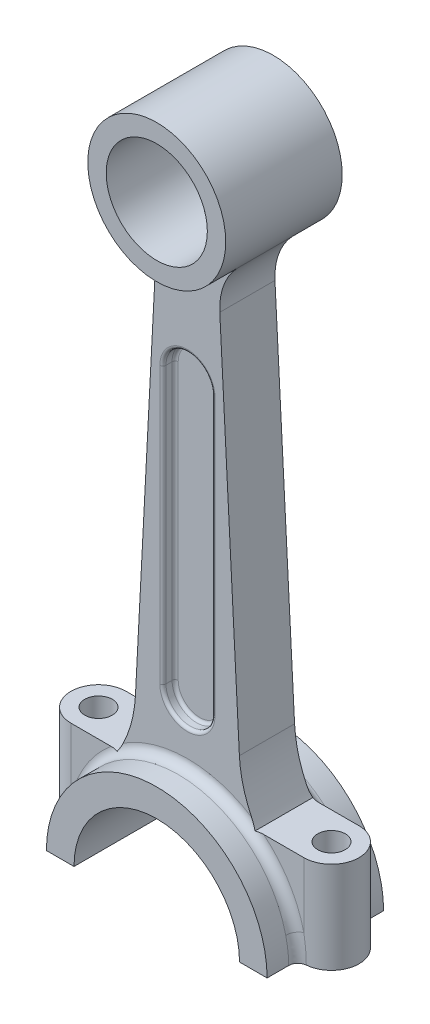
SolidWorks part; units mm, degrees
material "Alloy Steel (SS)"
ref_plane "Front Plane" through (0, 0, 0) normal (0, 0, 1) x (1, 0, 0)
ref_plane "Top Plane" through (0, 0, 0) normal (0, 1, 0) x (1, 0, 0)
ref_plane "Right Plane" through (0, 0, 0) normal (1, 0, 0) x (0, 0, -1)
sketch "Sketch2" plane through (0, 0, 0) normal (0, 0, 1) x (1, 0, 0)
  line L0 (-36, -201.2) -> (-27, -201.2)
  line L1 (27, -201.2) -> (36, -201.2)
  line L2 (0, 42.6594) -> (0, -201.2) construction
  line L3 (-10, -20.1556) -> (-17.85, -169.937)
  line L4 (10, -20.1556) -> (17.85, -169.937)
  circle A0 centre (0, 0) radius 22.5
  circle A1 centre (0, 0) radius 16.5
  arc A2 (36, -201.2) -> (-36, -201.2) centre (0, -201.2) ccw
  arc A3 (27, -201.2) -> (-27, -201.2) centre (0, -201.2) ccw
  point P6 (-17.85, -169.937)
  point P11 (17.85, -169.937)
  point P12 (-10, -20.1556)
  point P13 (10, -20.1556)
  dimension "D1" = 45
  dimension "D2" = 33
  dimension "D3" = 36
  dimension "D4" = 27
  dimension "D6" = 35.7
  dimension "D5" = 201.2
  dimension "D7" = 17.85
  dimension "D8" = 20
  dimension "D9" = 10
extrude "Boss-Extrude1" add sketch "Sketch2" along normal mid plane 38 contours L2 A0 A1 | A0 L2 A1 | A2 L2 A3 L1 | L2 A2 L0 A3 region at (-20.1899, -181.0101, 0) region at (20.1899, -181.0101, 0) region at (-21.4162, 5.0207, 0) region at (15.5541, 15.5541, 0)
extrude "Boss-Extrude2" add sketch "Sketch2<4>" along normal mid plane 18 contours A0 L2 A2 L4 | L2 A0 L3 A2 region at (-7.1844, -100.8457, 0) region at (7.1844, -100.8457, 0)
sketch "Sketch2<4>" plane through (0, 0, 0) normal (0, 0, 1) x (1, 0, 0) same geometry as "Sketch2"
sketch "Sketch3" plane through (0, 0, 9) normal (0, 0, 1) x (1, 0, 0)
  line L0 (0, -55.6) -> (0, -145.6) construction
  line L1 (8, -55.6) -> (8, -145.6)
  line L2 (-8, -55.6) -> (-8, -145.6)
  arc A0 (8, -55.6) -> (-8, -55.6) centre (0, -55.6) ccw
  arc A1 (-8, -145.6) -> (8, -145.6) centre (0, -145.6) ccw
  point P2 (0, -100.6)
  dimension "D1" = 8
  dimension "D2" = 90
  dimension "D3" = 100.6
extrude "Cut-Extrude1" cut sketch "Sketch3" against normal blind 4 contours A0 L2 A1 L1
mirror "Mirror1" about plane through (0, 0, 0) normal (0, 0, 1) of "Cut-Extrude1"
fillet "Fillet1" radius 1 16 edges at (0, -153.6, 5) (0, -153.6, 9) (-8, -100.6, 5) (-8, -100.6, 9) (8, -100.6, 5) (8, -100.6, 9) (0, -47.6, 5) (0, -47.6, 9) (0, -153.6, -5) (8, -100.6, -5) (-8, -100.6, -5) (0, -47.6, -5) (8, -100.6, -9) (0, -153.6, -9) (-8, -100.6, -9) (0, -47.6, -9)
fillet "Fillet2" radius 40 2 edges at (17.85, -169.937, 0) (-17.85, -169.937, 0)
fillet "Fillet3" radius 20.5 2 edges at (10, -20.1556, 0) (-10, -20.1556, 0)
ref_plane "Plane1" through (0, -171.2, 0) normal (0, -1, 0) x (-1, 0, 0)
sketch "Sketch4" plane through (0, -171.2, 0) normal (0, -1, 0) x (-1, 0, 0)
  line L0 (-38, 0) -> (38, 0) construction
  line L1 (-38, 9) -> (38, 9)
  line L2 (-38, -9) -> (38, -9)
  arc A0 (-38, 9) -> (-38, -9) centre (-38, 0) ccw
  arc A1 (38, -9) -> (38, 9) centre (38, 0) ccw
  point P2 (0, 0)
  dimension "D2" = 9
  dimension "D1" = 76
extrude "Boss-Extrude3" add sketch "Sketch4" along normal through all
sketch "Sketch5" plane through (0, 0, 9) normal (0, 0, 1) x (1, 0, 0)
  line L0 (-27, -201.2) -> (27, -201.2)
  arc A0 (-27, -201.2) -> (27, -201.2) centre (0, -201.2) cw
extrude "Cut-Extrude2" cut sketch "Sketch5" against normal up to surface (18 mm away) up to face at (0, -187.7, -9)
sketch "Sketch6" plane through (0, -171.2, 0) normal (0, -1, 0) x (-1, 0, 0)
  circle A0 centre (38, 0) radius 4.5
  circle A1 centre (-38, 0) radius 4.5
  dimension "D1" = 9
  dimension "D2" = 9
extrude "Cut-Extrude3" cut sketch "Sketch6" along direction (0, 1, 0) on the side of the normal through all contours A0 | A1
fillet "Fillet4" radius 3 2 edges at (0, -165.2, -9) (0, -165.2, 9)
